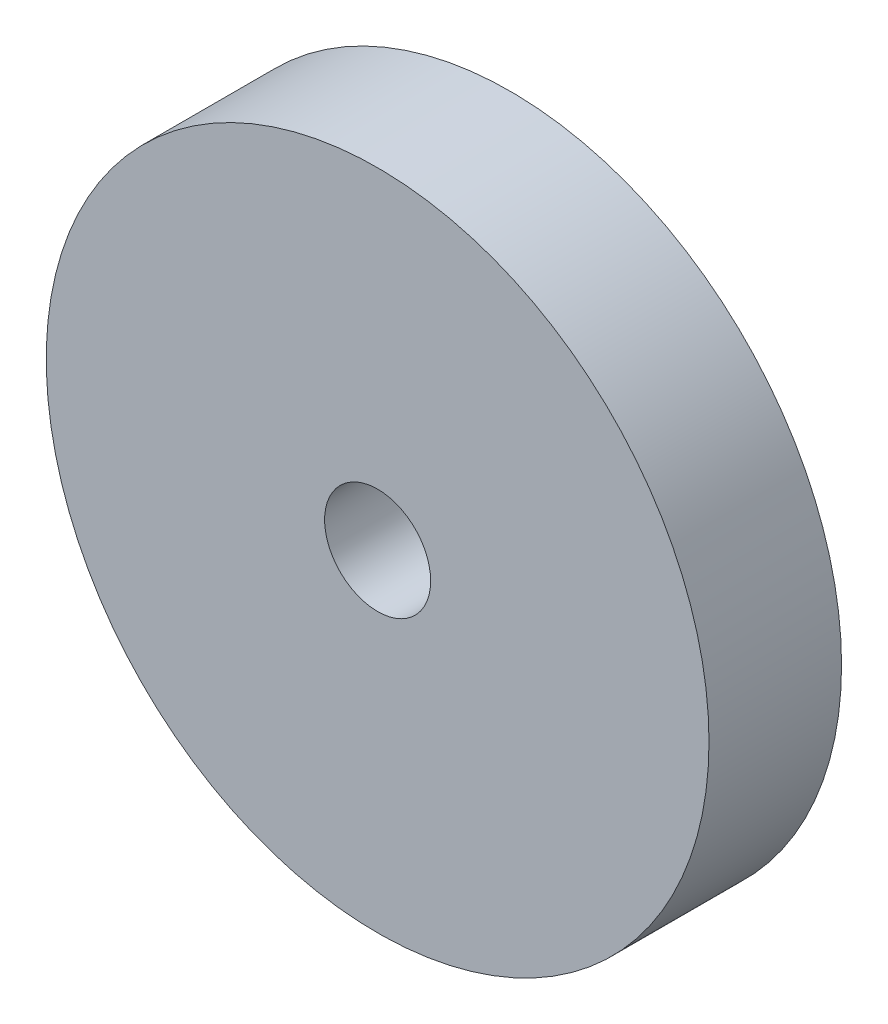
SolidWorks part; units mm, degrees
ref_plane "Front Plane" through (0, 0, 0) normal (0, 0, 1) x (1, 0, 0)
ref_plane "Top Plane" through (0, 0, 0) normal (0, 1, 0) x (1, 0, 0)
ref_plane "Right Plane" through (0, 0, 0) normal (1, 0, 0) x (0, 0, -1)
sketch "Sketch1" plane through (0, 0, 0) normal (0, 0, 1) x (1, 0, 0)
  circle A1 centre (-98.4636, -276.5051) radius 10
extrude "Boss-Extrude1" add sketch "Sketch1" along normal blind 4
hole_wizard "M3 Clearance Hole1" positions "Sketch3" profile "Sketch2" hole size "M3" standard "ISO" end condition through all
sketch "Sketch3" plane through (0, 0, 4) normal (0, 0, 1) x (1, 0, 0)
  point P0 (-98.4636, -276.5051)
sketch "Sketch2" plane through (-98.4636, -276.5051, 4) normal (1, 0, 0) x (0, -1, 0)
  line L0 (0, 0) -> (0, 4)
  line L1 (0, 4) -> (1.6, 4)
  line L2 (1.6, 4) -> (1.6, 0)
  line L5 (1.6, 0) -> (0, 0)
  line L11 (0, -6.35) -> (0, 107.95) construction
  dimension "Thru Hole Dia." = 3.2
  dimension "Thru Hole Depth" = 4
